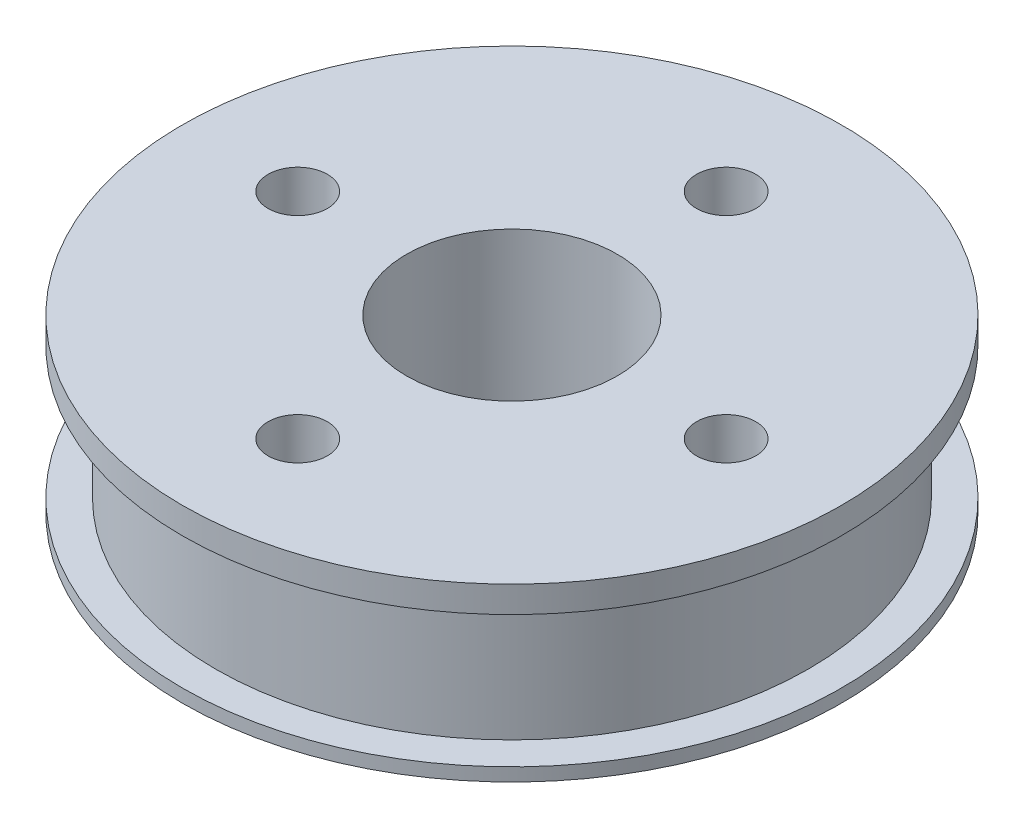
SolidWorks part; units mm, degrees
material "1060 Alloy"
ref_plane "Front Plane" through (0, 0, 0) normal (0, 0, 1) x (1, 0, 0)
ref_plane "Top Plane" through (0, 0, 0) normal (0, 1, 0) x (1, 0, 0)
ref_plane "Right Plane" through (0, 0, 0) normal (1, 0, 0) x (0, 0, -1)
sketch "Sketch1" plane through (0, 0, 0) normal (1, 0, 0) x (0, 0, -1)
  line L0 (0, 5.2515) -> (0, -4.6524) construction
  line L3 (22.5, 7.7982) -> (25, 7.7982)
  line L4 (8, -3.9621) -> (8, 7.7982)
  line L5 (8, 7.7982) -> (22.5, 7.7982)
  line L6 (22.5, -4.2018) -> (22.5, 5.7982)
  line L7 (22.5, -4.2018) -> (25, -4.2018)
  line L8 (8, -3.9621) -> (8, -5.2018)
  line L9 (8, -5.2018) -> (25, -5.2018)
  line L10 (25, -4.2018) -> (25, -5.2018)
  line L12 (22.5, 5.7982) -> (25, 5.7982)
  line L13 (25, 7.7982) -> (25, 5.7982)
  dimension "D2" = 22.5
  dimension "D1" = 8
  dimension "D3" = 25
  dimension "D4" = 13
  dimension "D5" = 1
  dimension "D6" = 2
  dimension "D7" = 2.5
revolve "Revolve1" add sketch "Sketch1" angle 360 about L0 region at (0, 1.362, -15.5753)
hole_wizard "Escareado para parafuso com cabeça escareada chata de M41" positions "Esboço2" profile "Esboço1" countersink size "M4" standard "ISO"
sketch "Esboço2" plane through (0, -5.2018, 0) normal (0, -1, 0) x (-1, 0, 0)
  circle A0 centre (0, 0) radius 16.25
  point P6 (0, 16.25)
  point P8 (-16.25, 0)
  point P10 (0, -16.25)
  point P12 (16.25, 0)
  dimension "D1" = 32.5
sketch "Esboço1" plane through (0, -5.2018, -16.25) normal (1, 0, 0) x (0, 0, -1)
  line L0 (0, 0) -> (0, 31.3519)
  line L1 (0, 31.3519) -> (2.25, 30)
  line L2 (2.25, 30) -> (2.25, 2.45)
  line L3 (2.25, 2.45) -> (4.7, 0)
  line L5 (4.7, 0) -> (0, 0)
  line L6 (-2.25, 2.45) -> (-4.7, 0) construction
  line L10 (0, 31.3519) -> (-2.25, 30) construction
  line L11 (0, -6.35) -> (0, 107.95) construction
  dimension "Hole Dia." = 4.5
  dimension "Hole Depth" = 30
  dimension "Near C'Sink Dia." = 9.4
  dimension "Near C'Sink Angle" = 90
  dimension "Drill Angle" = 118
